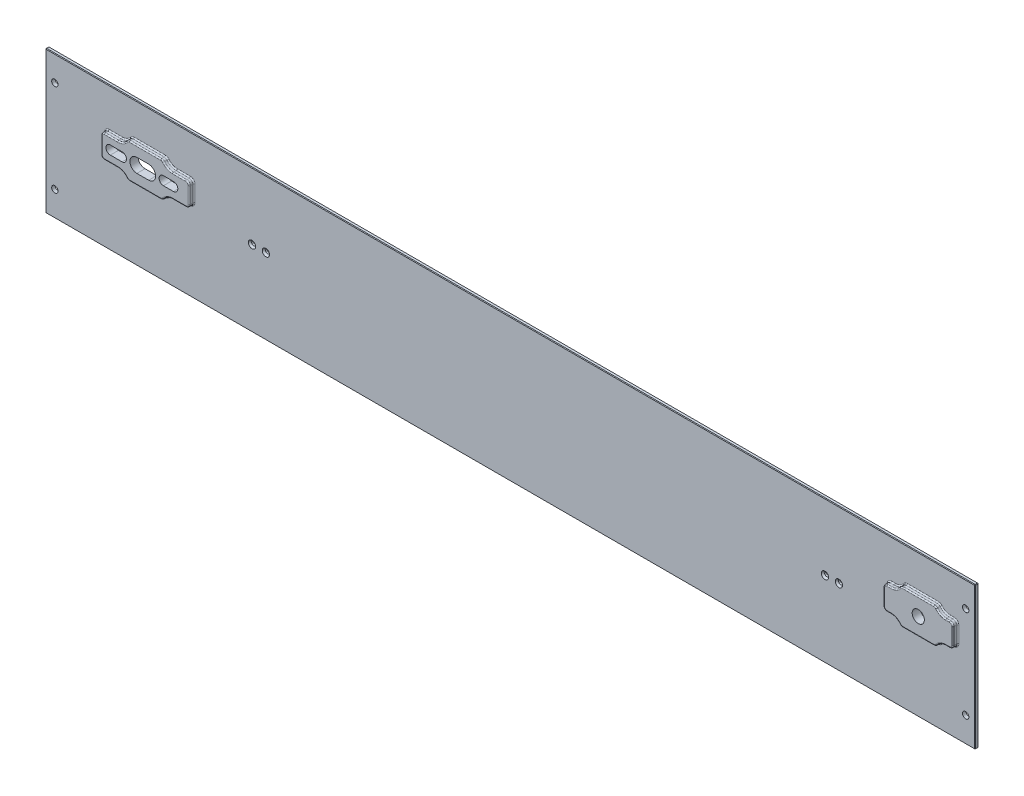
SolidWorks part; units mm, degrees
note: The reader was unsure of these and kept them because the rebuilt part matched: shared geometry of "Sketch4<2>".
ref_plane "Front Plane" through (0, 0, 0) normal (0, 0, 1) x (1, 0, 0)
ref_plane "Top Plane" through (0, 0, 0) normal (0, 1, 0) x (1, 0, 0)
ref_plane "Right Plane" through (0, 0, 0) normal (1, 0, 0) x (0, 0, -1)
sketch "Sketch1" plane through (0, 0, 0) normal (0, 0, 1) x (1, 0, 0)
  line L0 (-333.255, 17) -> (333.255, 17) construction
  line L1 (-423.255, 61) -> (378.255, 61)
  line L2 (-423.255, 61) -> (-423.255, -62)
  line L3 (-423.255, -62) -> (378.255, -62)
  line L4 (378.255, 61) -> (378.255, -62)
  line L5 (0, -17) -> (0, 17) construction
  line L7 (-333.255, -17) -> (333.255, -17) construction
  circle A0 centre (-333.255, 17) radius 6
  circle A1 centre (333.255, 17) radius 5.25
  point P0 (0, 0)
  point P9 (0, 0)
  point P14 (0, -17)
  dimension "D4" = 12
  dimension "D8" = 10.5
  dimension "D1" = 90
  dimension "D2" = 123
  dimension "D3" = 666.51
  dimension "D5" = 34
  dimension "D6" = 45
  dimension "D7" = 45
extrude "Boss-Extrude1" add sketch "Sketch1" along normal blind 3
sketch "Sketch4" plane through (0, 0, 3) normal (0, 0, 1) x (1, 0, 0)
  line L0 (-318.255, 27) -> (-295.255, 27)
  line L1 (-348.255, 32) -> (-318.255, 32)
  line L2 (-348.255, 32) -> (-348.255, 27)
  line L3 (-348.255, 2) -> (-318.255, 2)
  line L4 (-318.255, 32) -> (-318.255, 27)
  line L5 (-348.255, 32) -> (-318.255, 2) construction
  line L6 (-348.255, 2) -> (-318.255, 32) construction
  line L7 (318.255, 32) -> (348.255, 32)
  line L8 (318.255, 32) -> (318.255, 27)
  line L9 (318.255, 2) -> (348.255, 2)
  line L10 (348.255, 32) -> (348.255, 27)
  line L11 (318.255, 32) -> (348.255, 2) construction
  line L12 (318.255, 2) -> (348.255, 32) construction
  line L13 (-371.255, 27) -> (-348.255, 27)
  line L14 (-371.255, 27) -> (-371.255, 7)
  line L15 (-371.255, 7) -> (-348.255, 7)
  line L16 (-295.255, 27) -> (-295.255, 7)
  line L17 (-371.255, 27) -> (-295.255, 7) construction
  line L18 (-371.255, 7) -> (-295.255, 27) construction
  line L19 (-318.255, 7) -> (-295.255, 7)
  line L20 (-318.255, 7) -> (-318.255, 2)
  line L21 (-348.255, 7) -> (-348.255, 2)
  line L22 (348.255, 27) -> (363.255, 27)
  line L23 (303.255, 27) -> (318.255, 27)
  line L24 (303.255, 27) -> (303.255, 7)
  line L25 (303.255, 7) -> (318.255, 7)
  line L26 (363.255, 27) -> (363.255, 7)
  line L27 (303.255, 27) -> (363.255, 7) construction
  line L28 (303.255, 7) -> (363.255, 27) construction
  line L29 (348.255, 7) -> (348.255, 2)
  line L30 (348.255, 7) -> (363.255, 7)
  line L31 (318.255, 7) -> (318.255, 2)
  line L32 (-340.395, 23) -> (-330.255, 23)
  line L36 (-333.255, 17) -> (-355.395, 17) construction
  line L37 (-333.255, 17) -> (-311.115, 17) construction
  line L54 (-330.255, 11) -> (-340.395, 11)
  line L55 (-353.145, 17) -> (-363.285, 17) construction
  line L58 (-317.505, 17) -> (-308.865, 17) construction
  line L59 (-317.505, 20.75) -> (-308.865, 20.75)
  line L60 (-317.505, 13.25) -> (-308.865, 13.25)
  line L61 (-353.145, 13.25) -> (-363.285, 13.25)
  line L62 (-353.145, 20.75) -> (-363.285, 20.75)
  circle A12 centre (-311.115, 17) radius 3 construction
  circle A19 centre (-355.395, 17) radius 3 construction
  arc A23 (-340.395, 11) -> (-340.395, 23) centre (-340.395, 17) cw
  arc A26 (-317.505, 20.75) -> (-317.505, 13.25) centre (-317.505, 17) ccw
  arc A27 (-308.865, 13.25) -> (-308.865, 20.75) centre (-308.865, 17) ccw
  arc A28 (-330.255, 23) -> (-330.255, 11) centre (-330.255, 17) cw
  arc A29 (-353.145, 13.25) -> (-353.145, 20.75) centre (-353.145, 17) ccw
  arc A30 (-363.285, 20.75) -> (-363.285, 13.25) centre (-363.285, 17) ccw
  circle A32 centre (-333.255, 17) radius 6 construction
  point P0 (-333.255, 17)
  point P6 (333.255, 17)
  point P12 (-333.255, 17)
  point P21 (333.255, 17)
  point P38 (-358.215, 17)
  point P46 (-349.395, 17)
  point P49 (-313.185, 17)
  dimension "D17" = 7.5
  dimension "D15" = 6
  dimension "D14" = 6
  dimension "D10" = 3
  dimension "D16" = 3
  dimension "D19" = 3
  dimension "D20" = 3
  dimension "D21" = 3
  dimension "D1" = 30
  dimension "D2" = 30
  dimension "D3" = 30
  dimension "D4" = 30
  dimension "D5" = 23
  dimension "D6" = 20
  dimension "D7" = 15
  dimension "D8" = 20
  dimension "D9" = 12
  dimension "D11" = 22.14
  dimension "D12" = 22.14
  dimension "D13" = 7.5
  dimension "D18" = 10.14
extrude "Boss-Extrude2" add sketch "Sketch4" along normal blind 4
sketch "Sketch3" plane through (0, 0, 3) normal (0, 0, 1) x (1, 0, 0)
  line L0 (378.255, 39.25) -> (370.105, 39.25) construction
  line L1 (378.255, -62) -> (378.255, 61) construction
  line L2 (370.105, -0.5) -> (370.105, 39.25) construction
  line L3 (370.105, -0.5) -> (378.255, -0.5) construction
  line L4 (370.105, -0.5) -> (370.105, -40.25) construction
  circle A0 centre (370.105, 39.25) radius 2.75
  circle A1 centre (370.105, -40.25) radius 2.75
  dimension "D3" = 5.5
  dimension "D1" = 39.75
  dimension "D2" = 8.15
extrude "Cut-Extrude1" cut sketch "Sketch3" against normal through all both and the other way through all
ref_plane "Plane1" through (-22.5, 0, 0) normal (1, 0, 0) x (0, 0, -1)
mirror "Mirror3" about plane through (-22.5, 0, 0) normal (1, 0, 0) of "Cut-Extrude1"
fillet "Fillet1" radius 10 4 edges at (-318.255, 7, 5) (-348.255, 7, 5) (-348.255, 27, 5) (-318.255, 27, 5)
fillet "Fillet2" radius 3 8 edges at (-348.255, 2, 5) (-318.255, 2, 5) (-318.255, 32, 5) (-348.255, 32, 5) (-295.255, 27, 5) (-295.255, 7, 5) (-371.255, 7, 5) (-371.255, 27, 5)
fillet "Fillet3" radius 1 40 edges at (-352.53, 28.0128, 3) (-347.9839, 31.6962, 3) (-333.255, 32, 3) (-318.5261, 31.6962, 3) (-313.98, 28.0128, 3) (-303.9249, 27, 3) (-296.1337, 26.1213, 3) (-295.255, 17, 3) (-296.1337, 7.8787, 3) (-303.9249, 7, 3) (-313.98, 5.9872, 3) (-318.5261, 2.3038, 3) (-333.255, 2, 3) (-347.9839, 2.3038, 3) (-352.53, 5.9872, 3) (-362.5851, 7, 3) (-370.3763, 7.8787, 3) (-371.255, 17, 3) (-370.3763, 26.1213, 3) (-303.9249, 7, 7) (-362.5851, 27, 3) (-347.9839, 31.6962, 7) (-352.53, 28.0128, 7) (-362.5851, 27, 7) (-370.3763, 26.1213, 7) (-371.255, 17, 7) (-370.3763, 7.8787, 7) (-362.5851, 7, 7) (-352.53, 5.9872, 7) (-347.9839, 2.3038, 7) (-318.5261, 2.3038, 7) (-333.255, 2, 7) (-313.98, 5.9872, 7) (-296.1337, 7.8787, 7) (-295.255, 17, 7) (-296.1337, 26.1213, 7) (-303.9249, 27, 7) (-313.98, 28.0128, 7) (-318.5261, 31.6962, 7) (-333.255, 32, 7)
chamfer "Chamfer1" distance 0.5 angle 45 12 edges at (-22.5, 61, 0) (-423.255, -0.5, 0) (-423.255, -0.5, 3) (-423.255, -62, 1.5) (-22.5, -62, 3) (-22.5, -62, 0) (378.255, -62, 1.5) (378.255, -0.5, 3) (378.255, -0.5, 0) (378.255, 61, 1.5) (-22.5, 61, 3) (-423.255, 61, 1.5)
fillet "Fillet4" radius 10 4 edges at (348.255, 7, 5) (318.255, 7, 5) (318.255, 27, 5) (348.255, 27, 5)
fillet "Fillet5" radius 3 8 edges at (303.255, 7, 5) (318.255, 2, 5) (348.255, 2, 5) (363.255, 7, 5) (363.255, 27, 5) (348.255, 32, 5) (318.255, 32, 5) (303.255, 27, 5)
fillet "Fillet6" radius 1 40 edges at (318.5261, 31.6962, 7) (333.255, 32, 7) (347.9839, 31.6962, 7) (352.53, 28.0128, 7) (358.5851, 27, 7) (362.3763, 26.1213, 7) (363.255, 17, 7) (362.3763, 7.8787, 7) (358.5851, 7, 7) (352.53, 5.9872, 7) (347.9839, 2.3038, 7) (333.255, 2, 7) (318.5261, 2.3038, 7) (313.98, 5.9872, 7) (307.9249, 7, 7) (304.1337, 7.8787, 7) (303.255, 17, 7) (304.1337, 26.1213, 7) (307.9249, 27, 7) (307.9249, 27, 3) (304.1337, 26.1213, 3) (303.255, 17, 3) (304.1337, 7.8787, 3) (307.9249, 7, 3) (313.98, 5.9872, 3) (318.5261, 2.3038, 3) (333.255, 2, 3) (347.9839, 2.3038, 3) (352.53, 5.9872, 3) (358.5851, 7, 3) (362.3763, 7.8787, 3) (363.255, 17, 3) (362.3763, 26.1213, 3) (358.5851, 27, 3) (352.53, 28.0128, 3) (347.9839, 31.6962, 3) (333.255, 32, 3) (318.5261, 31.6962, 3) (313.98, 28.0128, 7) (313.98, 28.0128, 3)
extrude "Cut-Extrude2" cut sketch "Sketch4<2>" against normal through all
sketch "Sketch4<2>" plane through (0, 0, 3) normal (0, 0, 1) x (1, 0, 0) same geometry as "Sketch4"
sketch "Sketch5" plane through (0, 0, 3) normal (0, 0, -1) x (-1, 0, 0)
  circle A0 centre (-333.255, 17) radius 5.25
  circle A1 centre (-333.255, 17) radius 5.25 construction
extrude "Cut-Extrude3" cut sketch "Sketch5" against normal blind 10
sketch "Sketch6" plane through (0, 0, 0) normal (0, 0, -1) x (-1, 0, 0)
  circle A0 centre (-260.8631, 3.5) radius 1.5
  circle A1 centre (-248.8631, 3.5) radius 1.5
  circle A2 centre (233.1369, 3.5) radius 1.5
  circle A3 centre (245.1369, 3.5) radius 1.5
  point P0 (-260.8631, 3.5)
  point P3 (-248.8631, 3.5)
  point P7 (233.1369, 3.5)
  point P10 (245.1369, 3.5)
  dimension "D1" = 3
  dimension "D2" = 3
  dimension "D3" = 3
  dimension "D4" = 3
sketch "Sketch8" plane through (0, 0, 3) normal (0, 0, 1) x (1, 0, 0)
  line L0 (377.755, 60.5) -> (-422.755, 60.5) construction
  line L1 (377.755, -61.5) -> (377.755, 60.5) construction
  line L2 (-422.755, 60.5) -> (-422.755, -61.5) construction
  circle A0 centre (-233.1569, 3.5) radius 1.5
  circle A1 centre (-245.1569, 3.5) radius 1.5
  circle A2 centre (260.8431, 3.5) radius 1.5
  circle A3 centre (248.8431, 3.5) radius 1.5
  point P0 (-233.1569, 3.5)
  point P3 (-245.1569, 3.5)
  point P6 (260.8431, 3.5)
  point P9 (248.8431, 3.5)
  dimension "D8" = 3
  dimension "D9" = 177.5981
  dimension "D1" = 57
  dimension "D2" = 57
  dimension "D3" = 12
  dimension "D4" = 12
  dimension "D5" = 57
  dimension "D6" = 57
  dimension "D7" = 116.9119
hole_wizard "CSK for M3 Countersunk Flat Head Screw2" positions "Sketch8" profile "Sketch9" countersink size "M3" standard "ISO"
sketch "Sketch9" plane through (-233.1569, 3.5, 3) normal (1, 0, 0) x (0, -1, 0)
  line L0 (0, 0) -> (0, 31.0215)
  line L1 (0, 31.0215) -> (1.7, 30)
  line L2 (1.7, 30) -> (1.7, 1.45)
  line L3 (1.7, 1.45) -> (3.15, 0)
  line L5 (3.15, 0) -> (0, 0)
  line L6 (-1.7, 1.45) -> (-3.15, 0) construction
  line L10 (0, 31.0215) -> (-1.7, 30) construction
  line L11 (0, -6.35) -> (0, 107.95) construction
  dimension "Hole Dia." = 3.4
  dimension "Hole Depth" = 30
  dimension "Near C'Sink Dia." = 6.3
  dimension "Near C'Sink Angle" = 90
  dimension "Drill Angle" = 118
